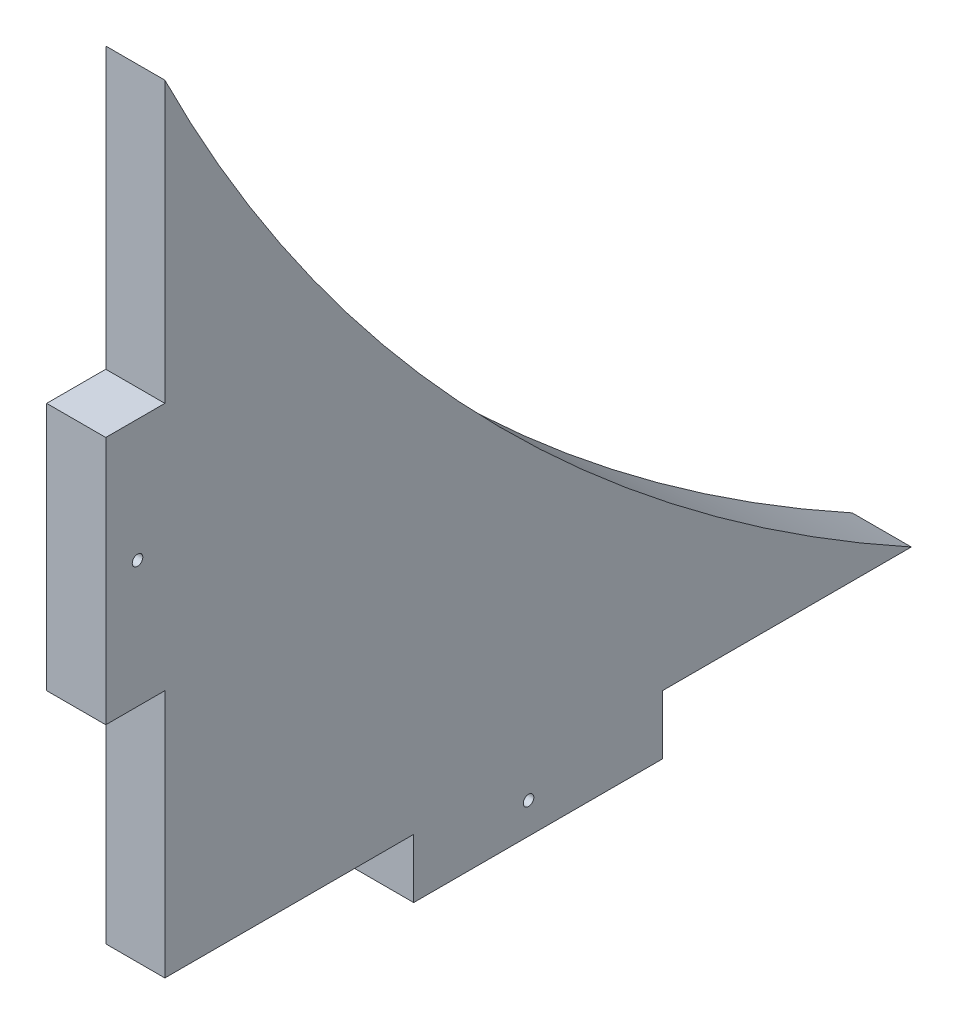
SolidWorks part; units mm, degrees
ref_plane "Front Plane" through (0, 0, 0) normal (0, 0, 1) x (1, 0, 0)
ref_plane "Top Plane" through (0, 0, 0) normal (0, 1, 0) x (1, 0, 0)
ref_plane "Right Plane" through (0, 0, 0) normal (1, 0, 0) x (0, 0, -1)
sketch "Sketch1" plane through (0, 0, 0) normal (1, 0, 0) x (0, 0, -1)
  line L0 (-143.7729, 109.4322) -> (-143.7729, -140.5678)
  line L1 (-143.7729, -140.5678) -> (96.2271, -140.5678)
  arc A0 (-143.7729, 109.4322) -> (96.2271, -140.5678) centre (373.8498, 366.15) ccw
  dimension "D1" = 250
  dimension "D2" = 240
extrude "Boss-Extrude1" add sketch "Sketch1" along normal blind 19
sketch "Sketch2" plane through (0, -140.5678, 0) normal (0, -1, 0) x (1, 0, 0)
  line L0 (0, 143.7729) -> (0, -96.2271) construction
  line L1 (0, 63.7729) -> (19, 63.7729)
  line L2 (0, 63.7729) -> (0, -16.2271)
  line L3 (0, -16.2271) -> (19, -16.2271)
  line L4 (19, 63.7729) -> (19, -16.2271)
  line L5 (19, 143.7729) -> (19, -96.2271) construction
  line L7 (19, 143.7729) -> (0, 143.7729) construction
  dimension "D2" = 80
extrude "Boss-Extrude2" add sketch "Sketch2" along normal blind 19
sketch "Sketch3" plane through (0, 0, 143.7729) normal (0, 0, 1) x (1, 0, 0)
  line L0 (0, 109.4322) -> (0, -140.5678) construction
  line L1 (0, 19.4322) -> (19, 19.4322)
  line L2 (0, 19.4322) -> (0, -60.5678)
  line L3 (0, -60.5678) -> (19, -60.5678)
  line L4 (19, 19.4322) -> (19, -60.5678)
  line L5 (19, 109.4322) -> (19, -140.5678) construction
  line L6 (19, -140.5678) -> (0, -140.5678) construction
  dimension "D1" = 80
extrude "Boss-Extrude3" add sketch "Sketch3" along normal blind 19
hole_wizard "M3 Clearance Hole1" positions "3DSketch1" profile "Sketch6" hole size "M3" standard "ISO" end condition through all
sketch3d "3DSketch1"
  point P0 (19, -19.8464, 152.5607)
  point P7 (19, -149.5769, 26.8466)
sketch "Sketch6" plane through (19, -19.8464, 152.5607) normal (0, 1, 0) x (0, 0, -1)
  line L0 (0, 0) -> (0, 19)
  line L1 (0, 19) -> (1.7, 19)
  line L2 (1.7, 19) -> (1.7, 0)
  line L5 (1.7, 0) -> (0, 0)
  line L11 (0, -6.35) -> (0, 107.95) construction
  dimension "Thru Hole Dia." = 3.4
  dimension "Thru Hole Depth" = 19
